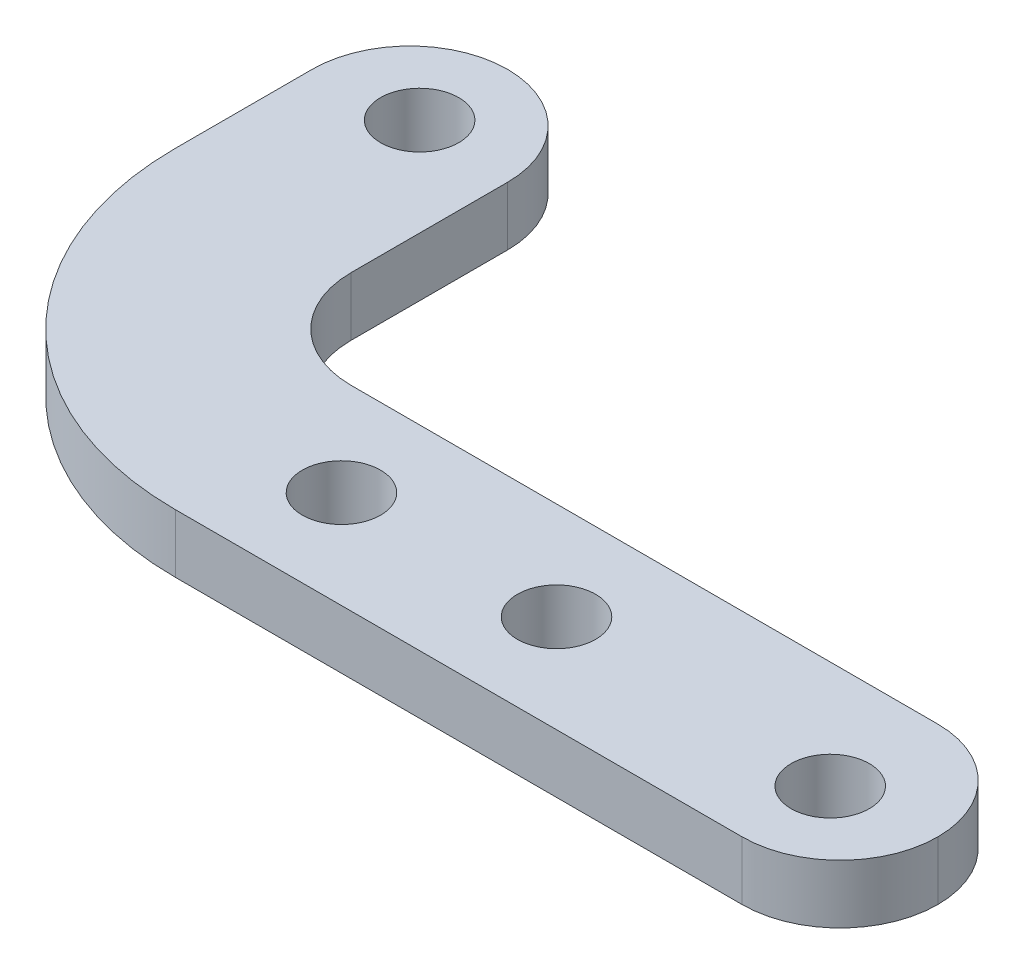
SolidWorks part; units mm, degrees
material "ABS PC"
ref_plane "Front Plane" through (0, 0, 0) normal (0, 0, 1) x (1, 0, 0)
ref_plane "Top Plane" through (0, 0, 0) normal (0, 1, 0) x (1, 0, 0)
ref_plane "Right Plane" through (0, 0, 0) normal (1, 0, 0) x (0, 0, -1)
sketch "Sketch1" plane through (0, 0, 0) normal (0, 1, 0) x (1, 0, 0)
  line L1 (25, -14) -> (-25, -14)
  line L2 (25, -14) -> (25, 14)
  line L3 (25, 14) -> (-25, 14)
  line L4 (-25, -14) -> (-25, 14)
  line L5 (25, -14) -> (-25, 14) construction
  line L6 (25, 14) -> (-25, -14) construction
  point P0 (0, 0)
  dimension "D1" = 28
  dimension "D2" = 50
extrude "Boss-Extrude1" add sketch "Sketch1" along normal blind 3
hole_wizard "Ø4.0 (4) Diameter Hole1" positions "Sketch2" profile "Sketch3" hole size "Ø4.0" standard "ANSI Metric" end condition through all
sketch "Sketch2" plane through (0, 3, 0) normal (0, 1, 0) x (1, 0, 0)
  line L1 (20, -9.5) -> (-20, -9.5)
  line L2 (20, -9.5) -> (20, 9.5)
  line L3 (20, 9.5) -> (-20, 9.5)
  line L4 (-20, -9.5) -> (-20, 9.5)
  line L5 (20, -9.5) -> (-20, 9.5) construction
  line L6 (20, 9.5) -> (-20, -9.5) construction
  line L7 (0, 14) -> (0, 0) construction
  line L8 (25, 14) -> (-25, 14) construction
  line L9 (0, 0) -> (0, -14) construction
  line L10 (-25, -14) -> (25, -14) construction
  point P2 (-20, 9.5)
  point P5 (20, -9.5)
  dimension "D1" = 19
  dimension "D2" = 40
sketch "Sketch3" plane through (-20, 3, -9.5) normal (1, 0, 0) x (0, 0, 1)
  line L0 (0, 0) -> (0, 3)
  line L1 (0, 3) -> (2, 3)
  line L2 (2, 3) -> (2, 0)
  line L5 (2, 0) -> (0, 0)
  line L11 (0, -6.35) -> (0, 107.95) construction
  dimension "Thru Hole Dia." = 4
  dimension "Thru Hole Depth" = 3
sketch "Sketch4" plane through (0, 3, 0) normal (0, 1, 0) x (1, 0, 0)
  line L0 (-25, -14) -> (25, -14) construction
  line L1 (9, -9) -> (-9, -9)
  line L2 (9, -9) -> (9, -14)
  line L3 (9, -14) -> (-9, -14)
  line L4 (-9, -9) -> (-9, -14)
  line L5 (9, -9) -> (-9, -14) construction
  line L6 (9, -14) -> (-9, -9) construction
  line L7 (0, -11.5) -> (0, 0) construction
  point P0 (0, -11.5)
  dimension "D1" = 18
  dimension "D2" = 5
extrude "Cut-Extrude1" [suppressed] cut sketch "Sketch4" against normal blind 3
hole_wizard "Ø4.0 (4) Diameter Hole2" positions "Sketch7" profile "Sketch8" hole size "Ø4.0" standard "ANSI Metric" end condition through all
sketch "Sketch7" plane through (0, 3, 0) normal (0, 1, 0) x (1, 0, 0)
  line L0 (0, 18.0075) -> (0, 15.2248) construction
  line L2 (-25, -14) -> (25, -14) construction
  point P0 (-5.5, -9)
  point P7 (5.5, -9)
  dimension "D1" = 11
  dimension "D2" = 5
sketch "Sketch8" plane through (-5.5, 3, 9) normal (1, 0, 0) x (0, 0, 1)
  line L0 (0, 0) -> (0, 3)
  line L1 (0, 3) -> (2, 3)
  line L2 (2, 3) -> (2, 0)
  line L5 (2, 0) -> (0, 0)
  line L11 (0, -6.35) -> (0, 107.95) construction
  dimension "Thru Hole Dia." = 4
  dimension "Thru Hole Depth" = 3
sketch "Sketch10" plane through (0, 3, 0) normal (0, 1, 0) x (1, 0, 0)
  line L0 (-15, 14) -> (-15, -4)
  line L1 (25, 14) -> (-25, 14) construction
  line L2 (-15, -4) -> (25, -4)
  line L3 (25, -14) -> (25, 14) construction
  line L4 (25, -4) -> (25, 14)
  line L5 (25, 14) -> (-15, 14)
  circle A0 centre (-20, 9.5) radius 2 construction
  circle A1 centre (5.5, -9) radius 2 construction
  dimension "D1" = 5
  dimension "D2" = 5
extrude "Cut-Extrude2" cut sketch "Sketch10" against normal blind 3
fillet "Fillet2" radius 5 5 edges at (25, 1.5, 4) (25, 1.5, 14) (-25, 1.5, -14) (-15, 1.5, -14) (-15, 1.5, 4)
fillet "Fillet3" radius 16 1 edges at (-25, 1.5, 14)
